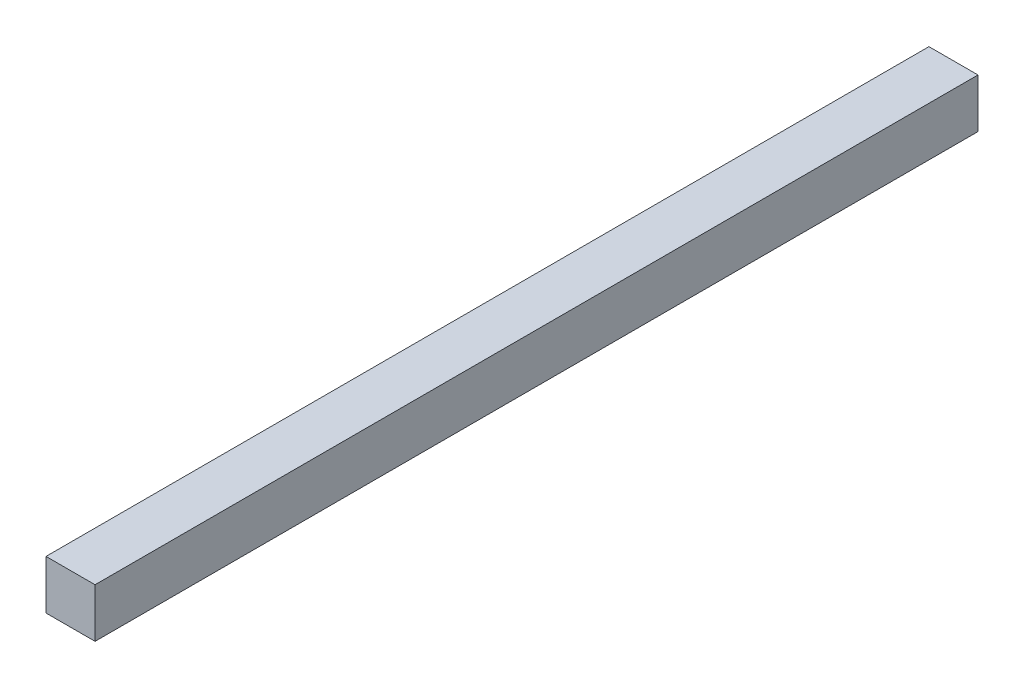
SolidWorks part; units mm, degrees
ref_plane "Front Plane" through (0, 0, 0) normal (0, 0, 1) x (1, 0, 0)
ref_plane "Top Plane" through (0, 0, 0) normal (0, 1, 0) x (1, 0, 0)
ref_plane "Right Plane" through (0, 0, 0) normal (1, 0, 0) x (0, 0, -1)
sketch "Sketch2" plane through (0, 0, 0) normal (0, 0, 1) x (1, 0, 0)
  line L1 (-12.7, -12.7) -> (12.7, -12.7)
  line L2 (-12.7, -12.7) -> (-12.7, 12.7)
  line L3 (-12.7, 12.7) -> (12.7, 12.7)
  line L4 (12.7, -12.7) -> (12.7, 12.7)
  line L5 (-12.7, -12.7) -> (12.7, 12.7) construction
  line L6 (-12.7, 12.7) -> (12.7, -12.7) construction
  point P0 (0, 0)
  dimension "D1" = 25.4
  dimension "D2" = 25.4
extrude "Boss-Extrude2" add sketch "Sketch2" along normal blind 457.2
